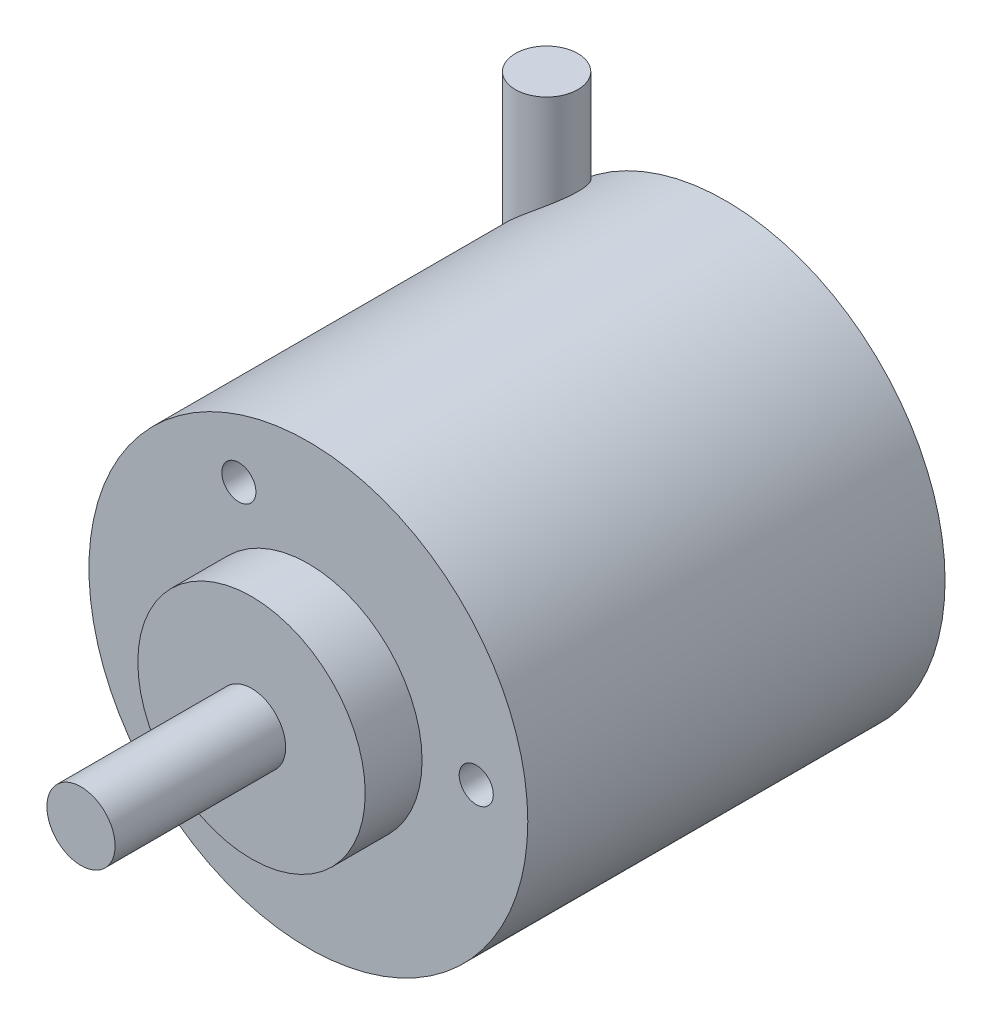
SolidWorks part; units mm, degrees
ref_plane "Front Plane" through (0, 0, 0) normal (0, 0, 1) x (1, 0, 0)
ref_plane "Top Plane" through (0, 0, 0) normal (0, 1, 0) x (1, 0, 0)
ref_plane "Right Plane" through (0, 0, 0) normal (1, 0, 0) x (0, 0, -1)
sketch "Sketch1" plane through (0, 0, 0) normal (0, 0, 1) x (1, 0, 0)
  circle A0 centre (-14.1274, 5.3793) radius 19.3
  dimension "D1" = 38.6
extrude "Boss-Extrude1" add sketch "Sketch1" along normal blind 36.7
sketch "Sketch3" plane through (0, 0, 36.7) normal (0, 0, 1) x (1, 0, 0)
  circle A0 centre (-14.1274, 5.3793) radius 10
  circle A1 centre (-14.1274, 5.3793) radius 19.3 construction
  dimension "D1" = 20
  dimension "D2" = 0
extrude "Boss-Extrude2" add sketch "Sketch3" along normal blind 5
sketch "Sketch4" plane through (0, 0, 41.7) normal (0, 0, 1) x (1, 0, 0)
  circle A0 centre (-14.1274, 5.3793) radius 3
  circle A1 centre (-14.1274, 5.3793) radius 10 construction
  dimension "D1" = 6
  dimension "D2" = 0
extrude "Boss-Extrude3" add sketch "Sketch4" along normal blind 15
sketch "Sketch5" plane through (0, 0, 36.7) normal (0, 0, 1) x (1, 0, 0)
  circle A0 centre (0.6377, 5.9084) radius 1.5
  dimension "D1" = 3
extrude "Cut-Extrude1" cut sketch "Sketch5" against normal blind 5
sketch "Sketch6" plane through (0, 0, 36.7) normal (0, 0, 1) x (1, 0, 0)
  circle A0 centre (-20.2402, 18.5215) radius 1.5
  dimension "D1" = 3
extrude "Cut-Extrude2" cut sketch "Sketch6" against normal blind 5 contours A0
sketch "Sketch7" plane through (0, 0, 36.7) normal (0, 0, 1) x (1, 0, 0)
  circle A0 centre (-20.269, -8.046) radius 1.5
  dimension "D1" = 3
extrude "Cut-Extrude3" cut sketch "Sketch7" against normal blind 5
ref_plane "Plane1" through (0, 24.6793, 0) normal (0, 1, 0) x (1, 0, 0)
sketch "Sketch8" plane through (0, 24.6793, 0) normal (0, 1, 0) x (1, 0, 0)
  circle A0 centre (-26.8321, -3.0426) radius 2.75
  dimension "D1" = 5.5
extrude "Boss-Extrude4" add sketch "Sketch8" against normal blind 15 separate body
sketch "Sketch9" plane through (0, 24.6793, 0) normal (0, 1, 0) x (1, 0, 0)
  circle A0 centre (-26.8321, -3.0426) radius 2.75
extrude "Boss-Extrude5" add sketch "Sketch9" along normal blind 5
